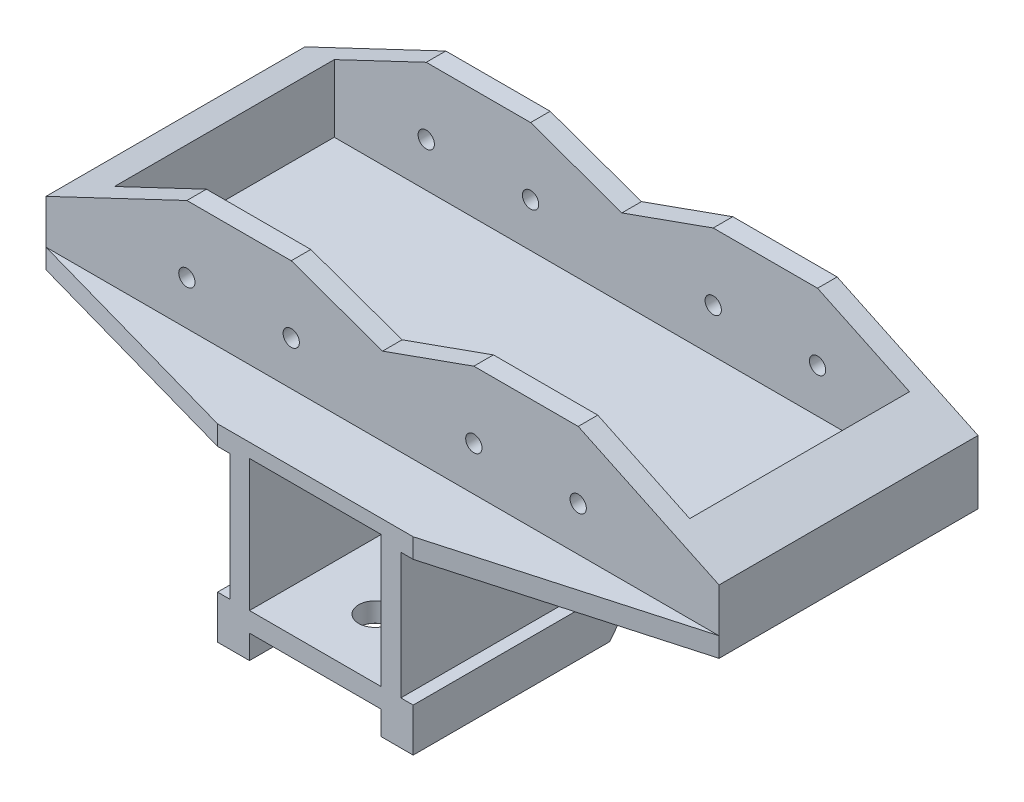
SolidWorks part; units mm, degrees
ref_plane "前视基准面" through (0, 0, 0) normal (0, 0, 1) x (1, 0, 0)
ref_plane "上视基准面" through (0, 0, 0) normal (0, 1, 0) x (1, 0, 0)
ref_plane "右视基准面" through (0, 0, 0) normal (1, 0, 0) x (0, 0, -1)
sketch "草图1" plane through (0, 0, 0) normal (0, 0, 1) x (1, 0, 0)
  line L0 (0, 0) -> (-103.2, 0)
  line L1 (-103.2, 0) -> (-103.2, 20)
  line L2 (-103.2, 20) -> (0, 20)
  line L3 (0, 20) -> (0, 0)
  dimension "D1" = 103.2
  dimension "D2" = 20
extrude "凸台-拉伸1" add sketch "草图1" along normal blind 39.7
sketch "草图2" plane through (0, 20, 0) normal (0, 1, 0) x (1, 0, 0)
  line L0 (-51.6, 0) -> (-51.6, -39.7) construction
  line L2 (-99.2, -19.85) -> (-72.6862, -19.85) construction
  line L5 (-95.7, -3) -> (-7.5, -3)
  line L6 (-95.7, -3) -> (-95.7, -36.7)
  line L7 (-95.7, -36.7) -> (-7.5, -36.7)
  line L8 (-7.5, -3) -> (-7.5, -36.7)
  dimension "D1" = 88.2
  dimension "D2" = 33.7
extrude "切除-拉伸1" cut sketch "草图2" against normal offset from surface (17 mm away) 3 up to face at (-51.6, 0, 19.85)
sketch "草图3" plane through (0, 0, 0) normal (0, -1, 0) x (1, 0, 0)
  line L6 (-51.6, 39.7) -> (-51.6, -13.7739) construction
  line L11 (-103.2, 0) -> (0, 0) construction
  line L12 (-66.6, 0) -> (-36.6, 0)
  line L15 (-66.6, 0) -> (-66.6, 50)
  line L16 (-66.6, 50) -> (-36.6, 50)
  line L17 (-36.6, 50) -> (-36.6, 0)
  point P11 (-51.6, 0)
  dimension "D1" = 50
  dimension "D2" = 15
extrude "凸台-拉伸2" add sketch "草图3" along normal blind 29 from offset 3 offset against normal yes
sketch "草图21" plane through (0, 0, 50) normal (0, 0, 1) x (1, 0, 0)
  line L0 (-7.5, 3) -> (-95.7, 3) construction
  line L1 (-7.5, 3) -> (-95.7, 3) construction
  line L2 (-98.033, -9.25) -> (-9.0097, -9.25) construction
  line L3 (-51.6, -26) -> (-51.6, 30.6239) construction
  line L4 (-61.7, 0.85) -> (-41.5, 0.85)
  line L5 (-61.7, 0.85) -> (-61.7, -19.35)
  line L6 (-61.7, -19.35) -> (-41.5, -19.35)
  line L7 (-41.5, 0.85) -> (-41.5, -19.35)
  dimension "D1" = 12.25
  dimension "D2" = 20.2
  dimension "D3" = 20.2
extrude "切除-拉伸11" cut sketch "草图21" against normal offset from surface (30.15 mm away) 19.85 up to face at (-51.6, -1.5, 0)
sketch "草图22" plane through (0, -26, 0) normal (0, -1, 0) x (1, 0, 0)
  line L1 (-61.7, 50) -> (-41.5, 50)
  line L2 (-41.5, 50) -> (-41.5, 0)
  line L3 (-66.6, 0) -> (-36.6, 0) construction
  line L4 (-41.5, 0) -> (-61.7, 0)
  line L5 (-61.7, 0) -> (-61.7, 50)
  line L6 (-36.6, 50) -> (-66.6, 50) construction
  dimension "D1" = 0
extrude "切除-拉伸12" cut sketch "草图22" against normal offset from surface (3.65 mm away) 3 up to face at (-51.6, -19.35, 34.925)
sketch "草图24" plane through (-36.6, 0, 0) normal (1, 0, 0) x (0, 0, -1)
  line L0 (0, 0) -> (0, -26)
  line L1 (0, -26) -> (-19.85, -26)
  line L2 (0, -26) -> (-50, -26) construction
  line L3 (-19.85, -26) -> (0, 0)
  line L4 (-19.85, -19.35) -> (-19.85, 0.85) construction
  line L5 (-19.85, -19.35) -> (-19.85, 0.85) construction
extrude "切除-拉伸14" cut sketch "草图24" against normal through all
sketch "草图25" plane through (0, 0, 0) normal (0, -1, 0) x (1, 0, 0)
  line L0 (-36.6, 39.7) -> (-36.6, 50)
  line L1 (-36.6, 50) -> (0, 39.7)
  line L2 (-51.6, 50) -> (-51.6, 41.294) construction
  line L4 (-36.6, 39.7) -> (0, 39.7)
  line L5 (-66.6, 39.7) -> (-103.2, 39.7)
  line L6 (-66.6, 50) -> (-103.2, 39.7)
  line L7 (-66.6, 39.7) -> (-66.6, 50)
extrude "凸台-拉伸4" add sketch "草图25" against normal up to surface (3 mm away) up to face at (-51.6, 3, 44.85)
hole_wizard "Ø2.5mm 暗销孔2" positions "草图26" profile "草图27" hole size "Ø2.5" standard "ISO" end condition through all
sketch "草图26" plane through (0, 0, 0) normal (0, 0, -1) x (-1, 0, 0)
  line L0 (-4.2264, 3) -> (108.8141, 3) construction
  line L2 (36.6, 0) -> (0, 0) construction
  line L3 (51.6, 0) -> (51.6, 22.298) construction
  point P8 (37.6, 9.75)
  point P10 (21.6, 9.75)
  point P23 (65.6, 9.75)
  point P24 (81.6, 9.75)
  dimension "D1" = 3
  dimension "D2" = 14
  dimension "D3" = 16
  dimension "D4" = 6.75
  dimension "D5" = 6.75
sketch "草图27" plane through (-81.6, 9.75, 0) normal (1, 0, 0) x (0, 1, 0)
  line L0 (0, 0) -> (0, 50)
  line L1 (0, 50) -> (1.25, 50)
  line L2 (1.25, 50) -> (1.25, 0.025)
  line L3 (1.25, 0.025) -> (1.275, 0)
  line L5 (1.275, 0) -> (0, 0)
  line L6 (-1.25, 0.025) -> (-1.275, 0) construction
  line L11 (0, -6.35) -> (0, 107.95) construction
  dimension "通孔孔直径" = 2.5
  dimension "通孔孔深度" = 50
  dimension "近端锥形沉头孔直径" = 2.55
  dimension "近端锥形沉头孔角度" = 90
hole_wizard "Ø5.0mm 暗销孔3" positions "草图28" profile "草图29" hole size "Ø5.0" standard "ISO" end condition up to next
sketch "草图28" plane through (0, -22.35, 0) normal (0, -1, 0) x (-1, 0, 0)
  line L0 (51.6, -17.0634) -> (51.6, -50) construction
  line L4 (41.5, -19.85) -> (61.7, -19.85) construction
  point P19 (51.6, -25.85)
  point P21 (51.6, -40.85)
  dimension "D1" = 6
  dimension "D2" = 15
sketch "草图29" plane through (-51.6, -22.35, 40.85) normal (1, 0, 0) x (0, 0, -1)
  line L0 (0, 0) -> (0, 3)
  line L1 (0, 3) -> (2.5, 3)
  line L2 (2.5, 3) -> (2.5, 0.025)
  line L3 (2.5, 0.025) -> (2.525, 0)
  line L5 (2.525, 0) -> (0, 0)
  line L6 (-2.5, 0.025) -> (-2.525, 0) construction
  line L11 (0, -6.35) -> (0, 107.95) construction
  dimension "通孔孔直径" = 5
  dimension "通孔孔深度" = 3
  dimension "近端锥形沉头孔直径" = 5.05
  dimension "近端锥形沉头孔角度" = 90
sketch "草图30" plane through (-36.6, 0, 0) normal (1, 0, 0) x (0, 0, -1)
  line L0 (0, 0) -> (-50, 0) construction
  line L1 (-50, 0) -> (2.5209, 0)
  line L4 (-50, -19.35) -> (-19.85, -19.35)
  line L5 (-50, 0.85) -> (-50, -19.35)
  line L6 (-19.85, 0.85) -> (-50, 0.85)
  line L7 (-19.85, -19.35) -> (-19.85, 0.85)
  line L8 (-50, -19.35) -> (2.5209, -19.35)
  line L9 (-50, 0) -> (-50, -19.35)
  line L11 (2.5209, -19.35) -> (2.5209, 0)
  dimension "D1" = 0
extrude "切除-拉伸15" cut sketch "草图30" against normal offset from surface (1.9 mm away) 3 up to face at (-41.5, -9.25, 34.925)
sketch "草图31" plane through (-66.6, 0, 0) normal (-1, 0, 0) x (0, 0, 1)
  line L4 (0, 0) -> (14.773, -19.35)
  line L5 (50, 0) -> (0, 0)
  line L6 (50, -19.35) -> (50, 0)
  line L7 (14.773, -19.35) -> (50, -19.35)
  line L8 (0, 0) -> (14.773, -19.35)
  line L9 (50, 0) -> (0, 0)
  line L10 (50, -19.35) -> (50, 0)
  line L11 (14.773, -19.35) -> (50, -19.35)
  dimension "D1" = 0
extrude "切除-拉伸16" cut sketch "草图31" against normal offset from surface (1.9 mm away) 3 up to face at (-61.7, -9.25, 34.925)
hole_wizard "Ø5.0mm 暗销孔4" positions "草图34" profile "草图33" hole size "Ø5.0" standard "ISO" end condition through all
sketch "草图34" plane through (-38.5, 0, 0) normal (1, 0, 0) x (0, 0, -1)
  line L2 (-43.9538, -9.25) -> (-19.6706, -9.25) construction
  line L5 (-19.85, 0.85) -> (-19.85, -19.35) construction
  point P10 (-25.85, -9.25)
  dimension "D1" = 6
sketch "草图33" plane through (-38.5, -9.25, 25.85) normal (0, 1, 0) x (0, 0, -1)
  line L0 (0, 0) -> (0, 64.7)
  line L1 (0, 64.7) -> (2.5, 64.7)
  line L2 (2.5, 64.7) -> (2.5, 0.025)
  line L3 (2.5, 0.025) -> (2.525, 0)
  line L5 (2.525, 0) -> (0, 0)
  line L6 (-2.5, 0.025) -> (-2.525, 0) construction
  line L11 (0, -6.35) -> (0, 107.95) construction
  dimension "通孔孔直径" = 5
  dimension "通孔孔深度" = 64.7
  dimension "近端锥形沉头孔直径" = 5.05
  dimension "近端锥形沉头孔角度" = 90
sketch "草图35" plane through (0, 0, 0) normal (0, 0, -1) x (-1, 0, 0)
  line L0 (21.6, 9.75) -> (37.6, 9.75) construction
  line L1 (21.6, 9.75) -> (21.6, 21.6918) construction
  line L2 (37.6, 9.75) -> (37.6, 21.6918) construction
  line L3 (0, 9.75) -> (21.6, 20)
  line L4 (0, 0) -> (0, 20) construction
  line L5 (21.6, 20) -> (0, 20)
  line L6 (0, 20) -> (0, 9.75)
  line L7 (0, 20) -> (103.2, 20) construction
  line L8 (51.6, 0) -> (51.6, 24.4852) construction
  line L10 (37.6, 20) -> (51.6, 15)
  line L11 (51.6, 15) -> (51.6, 20)
  line L12 (65.6, 20) -> (37.6, 20)
  line L13 (81.6, 20) -> (103.2, 20)
  line L14 (103.2, 9.75) -> (81.6, 20)
  line L15 (103.2, 20) -> (103.2, 9.75)
  line L16 (65.6, 20) -> (51.6, 15)
  line M17 (103.2, 0) -> (103.2, 20)
  line M18 (103.2, 20) -> (0, 20)
  dimension "D1" = 5
extrude "切除-拉伸19" cut sketch "草图35" against normal through all contours L14 M17 M18 | L6 L3 L5 | L16 L12 L10 region at (-96, 16.5833, 0)
hole_wizard "Ø2.5mm 暗销孔1" positions "草图9" profile "草图10" hole size "Ø2.5" standard "ISO" end condition through all
sketch "草图9" plane through (0, 0, 0) normal (0, 0, -1) x (-1, 0, 0)
  line L0 (51.6, 20) -> (51.6, -22.35) construction
  line L1 (24.6288, 3) -> (104.6858, 3) construction
  line L3 (38.5, 0) -> (0, 0) construction
  point P25 (37.6, 9.75)
  point P27 (21.6, 9.75)
  point P30 (65.6, 9.75)
  point P31 (81.6, 9.75)
  dimension "D1" = 3
  dimension "D2" = 14
  dimension "D3" = 16
  dimension "D4" = 6.75
  dimension "D5" = 6.75
sketch "草图10" plane through (-81.6, 9.75, 0) normal (1, 0, 0) x (0, 1, 0)
  line L0 (0, 0) -> (0, 50)
  line L1 (0, 50) -> (1.25, 50)
  line L2 (1.25, 50) -> (1.25, 0.025)
  line L3 (1.25, 0.025) -> (1.275, 0)
  line L5 (1.275, 0) -> (0, 0)
  line L6 (-1.25, 0.025) -> (-1.275, 0) construction
  line L11 (0, -6.35) -> (0, 107.95) construction
  dimension "通孔孔直径" = 2.5
  dimension "通孔孔深度" = 50
  dimension "近端锥形沉头孔直径" = 2.55
  dimension "近端锥形沉头孔角度" = 90
